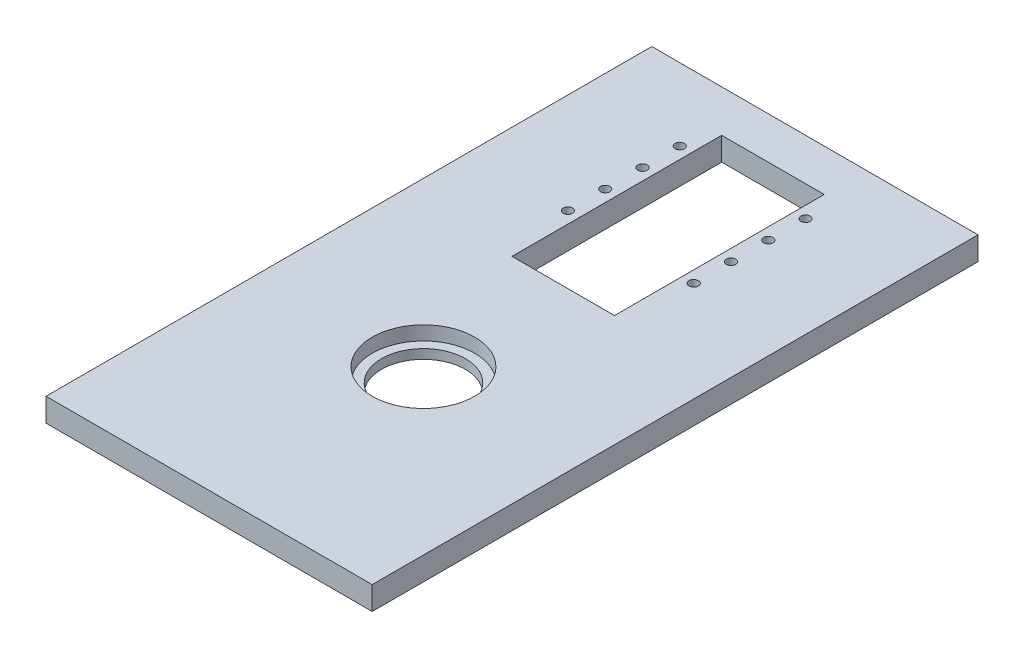
SolidWorks part; units mm, degrees
ref_plane "Front Plane" through (0, 0, 0) normal (0, 0, 1) x (1, 0, 0)
ref_plane "Top Plane" through (0, 0, 0) normal (0, 1, 0) x (1, 0, 0)
ref_plane "Right Plane" through (0, 0, 0) normal (1, 0, 0) x (0, 0, -1)
sketch "Sketch3" plane through (0, 0, 0) normal (0, 1, 0) x (1, 0, 0)
  line L0 (-13.5, 60.5) -> (-13.5, 52.5) construction
  line L1 (13.5, 60.5) -> (13.5, 52.5) construction
  line L2 (-13.5, 60.5) -> (-13.5, 68.5) construction
  line L3 (0, 38) -> (0, 0) construction
  line L4 (-35, 84) -> (35, 84)
  line L5 (-35, 84) -> (-35, -46)
  line L6 (-35, -46) -> (35, -46)
  line L7 (35, 84) -> (35, -46)
  line L8 (-35, 84) -> (35, -46) construction
  line L9 (-35, -46) -> (35, 84) construction
  line L11 (-11, 75) -> (11, 75)
  line L12 (-11, 75) -> (-11, 30)
  line L13 (-11, 30) -> (11, 30)
  line L14 (11, 75) -> (11, 30)
  line L15 (-11, 75) -> (11, 30) construction
  line L16 (-11, 30) -> (11, 75) construction
  circle A0 centre (-13.5, 60.5) radius 1
  circle A1 centre (13.5, 60.5) radius 1
  circle A2 centre (-13.5, 52.5) radius 1
  circle A3 centre (-13.5, 44.5) radius 1
  circle A4 centre (13.5, 52.5) radius 1
  circle A5 centre (13.5, 44.5) radius 1
  circle A6 centre (-13.5, 68.5) radius 1
  circle A7 centre (13.5, 68.5) radius 1
  circle A18 centre (0, 38) radius 13 construction
  circle A19 centre (0, 0) radius 25 construction
  circle A20 centre (0, 0) radius 9
  point P12 (0, 19)
  point P27 (0, 52.5)
  point P35 (0, 0)
  point P36 (0, 38)
  point P37 (0, 52.5)
  dimension "D1" = 2
  dimension "D11" = 130
  dimension "D12" = 6.5
  dimension "D14" = 50
  dimension "D15" = 26
  dimension "D13" = 18
  dimension "D2" = 27
  dimension "D3" = 13.5
  dimension "D4" = 70
  dimension "D6" = 8
  dimension "D8" = 8
  dimension "D10" = 8
  dimension "D16" = 45
  dimension "D17" = 22
  dimension "D18" = 30
  dimension "D5" = 3
  dimension "D7" = 3
  dimension "D9" = 2
extrude "Boss-Extrude1" add sketch "Sketch3" along normal blind 5
sketch "Sketch4" plane through (0, 5, 0) normal (0, 1, 0) x (1, 0, 0)
  circle A0 centre (0, 0) radius 11
  dimension "D1" = 22
extrude "Cut-Extrude3" cut sketch "Sketch4" against normal blind 3
